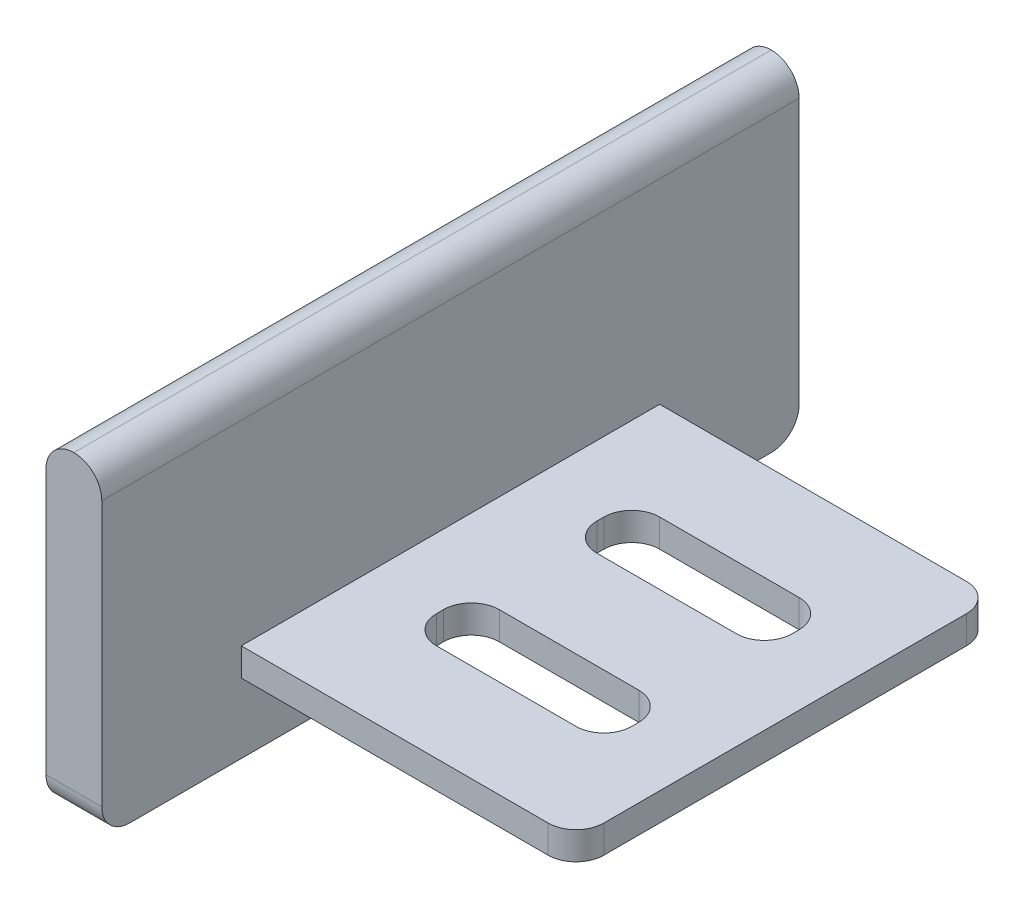
SolidWorks part; units mm, degrees
ref_plane "前视基准面" through (0, 0, 0) normal (0, 0, 1) x (1, 0, 0)
ref_plane "上视基准面" through (0, 0, 0) normal (0, 1, 0) x (1, 0, 0)
ref_plane "右视基准面" through (0, 0, 0) normal (1, 0, 0) x (0, 0, -1)
sketch "草图1" plane through (0, 0, 0) normal (0, 0, 1) x (1, 0, 0)
  line L0 (-4.7846, 19.3385) -> (-4.7846, -3.6615)
  line L1 (-4.7846, -3.6615) -> (-0.7846, -3.6615)
  line L2 (-0.7846, -3.6615) -> (-0.7846, 1.3385)
  line L3 (-0.7846, 1.3385) -> (23.2154, 1.3385)
  line L4 (23.2154, 1.3385) -> (23.2154, 3.3385)
  line L5 (23.2154, 3.3385) -> (-0.7846, 3.3385)
  line L6 (-0.7846, 3.3385) -> (-0.7846, 19.3385)
  line L7 (-0.7846, 19.3385) -> (-4.7846, 19.3385)
  dimension "D1" = 2
  dimension "D2" = 5
  dimension "D3" = 4
  dimension "D4" = 4
  dimension "D5" = 24
  dimension "D6" = 16
extrude "凸台-拉伸1" add sketch "草图1" along normal blind 50
sketch "草图2" plane through (0, 3.3385, 0) normal (0, 1, 0) x (1, 0, 0)
  line L0 (-0.7846, -50) -> (-0.7846, -40)
  line L1 (-0.7846, -50) -> (-0.7846, 0) construction
  line L2 (-0.7846, -40) -> (23.2154, -40)
  line L3 (23.2154, -50) -> (23.2154, 0) construction
  line L4 (23.2154, -40) -> (23.2154, -50)
  line L5 (23.2154, -50) -> (-0.7846, -50)
  line L7 (4.2154, -33) -> (18.2154, -33)
  line L8 (18.2154, -33) -> (18.2154, -28.5)
  line L9 (18.2154, -28.5) -> (4.2154, -28.5)
  line L10 (4.2154, -28.5) -> (4.2154, -33)
  line L11 (4.2154, -21.5) -> (4.2154, -17)
  line L12 (18.2154, -21.5) -> (4.2154, -21.5)
  line L13 (18.2154, -17) -> (18.2154, -21.5)
  line L14 (4.2154, -17) -> (18.2154, -17)
  line L15 (23.2154, 0) -> (-0.7846, 0)
  line L16 (23.2154, -10) -> (23.2154, 0)
  line L17 (-0.7846, -10) -> (23.2154, -10)
  line L18 (-0.7846, 0) -> (-0.7846, -10)
  dimension "D1" = 10
  dimension "D2" = 7
  dimension "D4" = 5
  dimension "D5" = 5
extrude "切除-拉伸1" cut sketch "草图2" against normal blind 50
fillet "圆角1" radius 2 1 edges at (23.2154, 2.3385, 40) type face fillet first side face at (11.2154, 2.3385, 40) second side face at (23.2154, 2.3385, 25)
fillet "圆角2" radius 2 1 edges at (23.2154, 2.3385, 10) type face fillet first side face at (11.2154, 2.3385, 10) second side face at (23.2154, 2.3385, 24)
fillet "圆角3" radius 2 1 edges at (4.2154, 2.3385, 28.5) type face fillet first side face at (4.2154, 2.3385, 30.75) second side face at (11.2154, 2.3385, 28.5)
fillet "圆角4" radius 2 1 edges at (4.2154, 2.3385, 33) type face fillet first side face at (4.2154, 2.3385, 31.75) second side face at (11.2154, 2.3385, 33)
fillet "圆角5" radius 2 1 edges at (4.2154, 2.3385, 17) type face fillet first side face at (11.2154, 2.3385, 17) second side face at (4.2154, 2.3385, 19.25)
fillet "圆角6" radius 2 1 edges at (4.2154, 2.3385, 21.5) type face fillet first side face at (11.2154, 2.3385, 21.5) second side face at (4.2154, 2.3385, 20.25)
fillet "圆角7" radius 2 1 edges at (18.2154, 2.3385, 17) type face fillet first side face at (12.2154, 2.3385, 17) second side face at (18.2154, 2.3385, 19.25)
fillet "圆角8" radius 2 1 edges at (18.2154, 2.3385, 33) type face fillet first side face at (12.2154, 2.3385, 33) second side face at (18.2154, 2.3385, 30.75)
fillet "圆角9" radius 2 1 edges at (18.2154, 2.3385, 28.5) type face fillet first side face at (12.2154, 2.3385, 28.5) second side face at (18.2154, 2.3385, 29.75)
fillet "圆角10" radius 2 1 edges at (18.2154, 2.3385, 21.5) type face fillet first side face at (18.2154, 2.3385, 20.25) second side face at (12.2154, 2.3385, 21.5)
fillet "圆角11" radius 2 1 edges at (-0.7846, 19.3385, 25) type face fillet first side face at (-0.7846, 7.8385, 25) second side face at (-2.7846, 19.3385, 25)
fillet "圆角12" radius 2 1 edges at (-4.7846, 19.3385, 25) type face fillet first side face at (-3.7846, 19.3385, 25) second side face at (-4.7846, 7.8385, 25)
fillet "圆角14" radius 2 1 edges at (-2.7846, -3.6615, 50) type face fillet first side face at (-2.7846, 9.5041, 50) second side face at (-2.7846, -3.6615, 25)
fillet "圆角15" radius 2 1 edges at (-2.7846, -3.6615, 0) type face fillet first side face at (-2.7846, -3.6615, 24) second side face at (-2.7846, 9.5041, 0)
sketch "草图3" plane through (0, -3.6615, 0) normal (0, -1, 0) x (1, 0, 0)
  line L0 (-4.7846, 48) -> (-4.7846, 2) construction
  line L1 (-0.7846, 0) -> (-4.7846, 0) construction
  line L2 (-4.7846, 50) -> (-0.7846, 50) construction
  circle A0 centre (-2.7846, 42.5) radius 1
  circle A1 centre (-2.7846, 7.5) radius 1
  dimension "D1" = 7.5
  dimension "D2" = 2
  dimension "D3" = 7.5
extrude "切除-拉伸2" cut sketch "草图3" against normal blind 7
